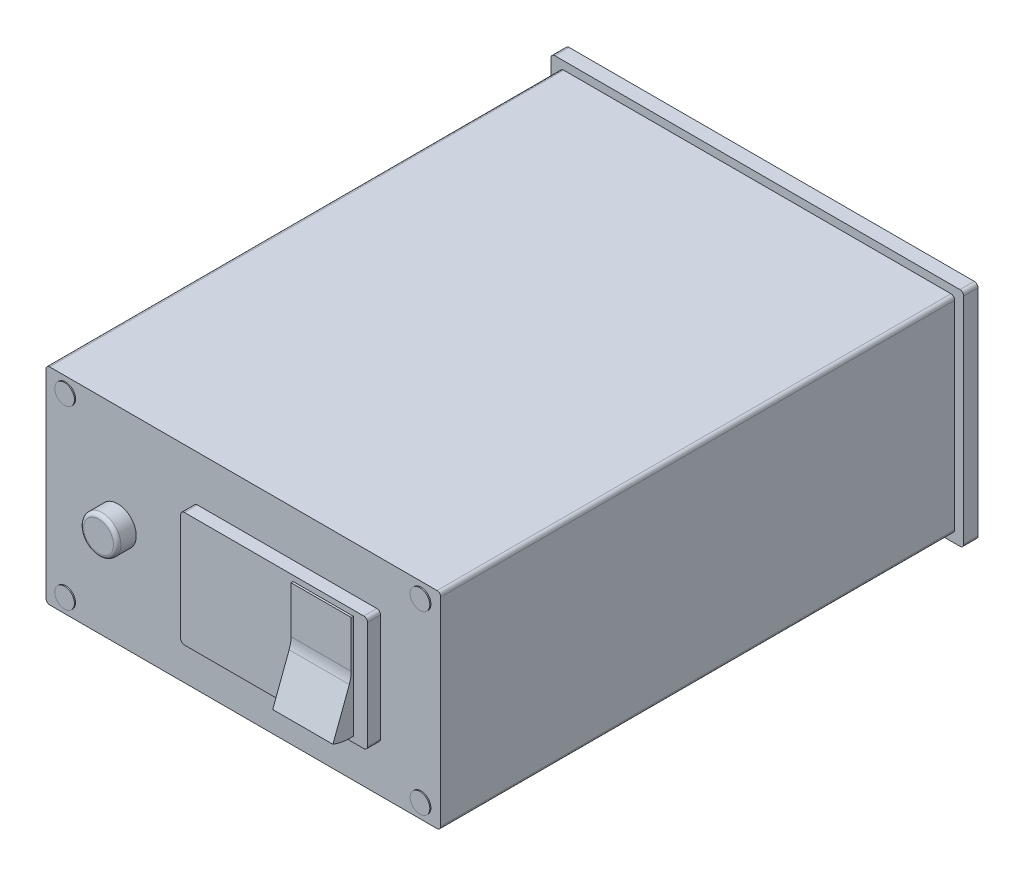
SolidWorks part; units mm, degrees
ref_plane "Front" through (0, 0, 0) normal (0, 0, 1) x (1, 0, 0)
ref_plane "Top" through (0, 0, 0) normal (0, 1, 0) x (1, 0, 0)
ref_plane "Right" through (0, 0, 0) normal (1, 0, 0) x (0, 0, -1)
sketch "Sketch1" plane through (0, 0, 0) normal (0, 0, 1) x (1, 0, 0)
  line L1 (-55.53, -29.925) -> (55.53, -29.925)
  line L2 (-55.53, -29.925) -> (-55.53, 29.925)
  line L3 (-55.53, 29.925) -> (55.53, 29.925)
  line L4 (55.53, -29.925) -> (55.53, 29.925)
  line L5 (-55.53, -29.925) -> (55.53, 29.925) construction
  line L6 (-55.53, 29.925) -> (55.53, -29.925) construction
  point P0 (0, 0)
  dimension "D1" = 59.85
  dimension "D2" = 111.06
extrude "Face" add sketch "Sketch1" along normal blind 3.86
fillet "Face Fillets" radius 1 4 edges at (-55.53, 29.925, 1.93) (-55.53, -29.925, 1.93) (55.53, -29.925, 1.93) (55.53, 29.925, 1.93)
sketch "Sketch2" plane through (0, 0, 0) normal (0, 0, 1) x (1, 0, 0)
  line L1 (-53.125, -27.75) -> (53.125, -27.75)
  line L2 (-53.125, -27.75) -> (-53.125, 27.75)
  line L3 (-53.125, 27.75) -> (53.125, 27.75)
  line L4 (53.125, -27.75) -> (53.125, 27.75)
  line L5 (-53.125, -27.75) -> (53.125, 27.75) construction
  line L6 (-53.125, 27.75) -> (53.125, -27.75) construction
  point P0 (0, 0)
  dimension "D1" = 106.25
  dimension "D2" = 55.5
extrude "Body" add sketch "Sketch2" along normal blind 142.2
sketch "Sketch3" plane through (0, -27.75, 0) normal (0, -1, 0) x (1, 0, 0)
  line L0 (-54.53, 3.86) -> (54.53, 3.86) construction
  line L1 (-36.625, 18.86) -> (36.625, 18.86) construction
  line L2 (-36.625, 18.86) -> (-36.625, 123.95) construction
  line L3 (-36.625, 123.95) -> (36.625, 123.95) construction
  line L4 (36.625, 18.86) -> (36.625, 123.95) construction
  line L5 (-36.625, 18.86) -> (36.625, 123.95) construction
  line L6 (-36.625, 123.95) -> (36.625, 18.86) construction
  line L7 (-53.125, 142.2) -> (53.125, 142.2) construction
  line L9 (-43, 117.575) -> (-30.25, 117.575)
  line L10 (-43, 117.575) -> (-43, 130.325)
  line L11 (-43, 130.325) -> (-30.25, 130.325)
  line L12 (-30.25, 117.575) -> (-30.25, 130.325)
  line L13 (-43, 117.575) -> (-30.25, 130.325) construction
  line L14 (-43, 130.325) -> (-30.25, 117.575) construction
  line L15 (30.25, 117.575) -> (43, 117.575)
  line L16 (30.25, 117.575) -> (30.25, 130.325)
  line L17 (30.25, 130.325) -> (43, 130.325)
  line L18 (43, 117.575) -> (43, 130.325)
  line L19 (30.25, 117.575) -> (43, 130.325) construction
  line L20 (30.25, 130.325) -> (43, 117.575) construction
  line L21 (30.25, 12.485) -> (43, 12.485)
  line L22 (30.25, 12.485) -> (30.25, 25.235)
  line L23 (30.25, 25.235) -> (43, 25.235)
  line L24 (43, 12.485) -> (43, 25.235)
  line L25 (30.25, 12.485) -> (43, 25.235) construction
  line L26 (30.25, 25.235) -> (43, 12.485) construction
  line L27 (-43, 12.485) -> (-30.25, 12.485)
  line L28 (-43, 12.485) -> (-43, 25.235)
  line L29 (-43, 25.235) -> (-30.25, 25.235)
  line L30 (-30.25, 12.485) -> (-30.25, 25.235)
  line L31 (-43, 12.485) -> (-30.25, 25.235) construction
  line L32 (-43, 25.235) -> (-30.25, 12.485) construction
  point P0 (0, 71.405)
  dimension "D1" = 15
  dimension "D2" = 18.25
  dimension "D3" = 73.25
  dimension "D4" = 12.75
extrude "Feet" add sketch "Sketch3" along normal blind 3.33 draft 25
fillet "Body Fillets" radius 1 4 edges at (53.125, 27.75, 73.03) (53.125, -27.75, 73.03) (-53.125, -27.75, 73.03) (-53.125, 27.75, 73.03)
sketch "Sketch4" plane through (0, 0, 142.2) normal (0, 0, 1) x (1, 0, 0)
  line L0 (-53.125, 26.75) -> (-53.125, -26.75) construction
  circle A0 centre (-33.825, 0) radius 5
  dimension "D1" = 10
  dimension "D2" = 19.3
extrude "GND Bannana Port" add sketch "Sketch4" along normal blind 5.15
fillet "Fillet3" radius 1 1 edges at (-28.825, 0, 147.35)
sketch "Sketch5" plane through (0, 0, 142.2) normal (0, 0, 1) x (1, 0, 0)
  line L0 (53.125, -26.75) -> (53.125, 26.75) construction
  line L1 (-13.375, -15.45) -> (36.925, -15.45)
  line L2 (-13.375, -15.45) -> (-13.375, 15.45)
  line L3 (-13.375, 15.45) -> (36.925, 15.45)
  line L4 (36.925, -15.45) -> (36.925, 15.45)
  line L5 (-13.375, -15.45) -> (36.925, 15.45) construction
  line L6 (-13.375, 15.45) -> (36.925, -15.45) construction
  point P0 (11.775, 0)
  dimension "D1" = 50.3
  dimension "D2" = 30.9
  dimension "D3" = 16.2
extrude "Power Port" add sketch "Sketch5" along normal blind 3.5
fillet "Fillet4" radius 1 4 edges at (-13.375, 15.45, 143.95) (-13.375, -15.45, 143.95) (36.925, -15.45, 143.95) (36.925, 15.45, 143.95)
ref_plane "Switch Plane" through (25, 0, 0) normal (1, 0, 0) x (0, 0, -1)
sketch "Sketch6" plane through (25, 0, 0) normal (1, 0, 0) x (0, 0, -1)
  line L0 (-146.274, 14) -> (-146.274, 1.4325)
  line L1 (-146.787, -1.3862) -> (-151.2, -13.1082)
  line L2 (-146.2832, 0) -> (-146.4033, 0) construction
  line L3 (-145.7, -14.45) -> (-145.7, 14.45) construction
  circle A0 centre (-146.2832, 0) radius 14 construction
  arc A1 (-146.274, 1.4325) -> (-146.787, -1.3862) centre (-154.274, 1.4325) cw
  arc A2 (-146.274, 14) -> (-151.2, -13.1082) centre (-146.2832, 0) cw
  point P4 (0, 0)
  point P8 (-146.259, 12.899)
  dimension "D1" = 28
  dimension "D2" = 8
  dimension "D3" = 5.5
extrude "Boss-Extrude6" add sketch "Sketch6" along normal mid plane 16.2
sketch "Sketch7" plane through (0, 0, 0) normal (0, 0, -1) x (-1, 0, 0)
  line L0 (-55.53, -28.925) -> (-55.53, 28.925) construction
  line L1 (54.53, -29.925) -> (-54.53, -29.925) construction
  circle A0 centre (-34.53, -2.925) radius 6.5
  dimension "D1" = 13
  dimension "D2" = 21
  dimension "D3" = 27
extrude "Boss-Extrude7" add sketch "Sketch7" along normal mid plane 4.7
sketch "Sketch8" plane through (0, 0, 142.2) normal (0, 0, 1) x (1, 0, 0)
  line L0 (-53.125, 26.75) -> (-53.125, -26.75) construction
  line L1 (52.125, 27.75) -> (-52.125, 27.75) construction
  circle A0 centre (-47.825, 23.75) radius 2.65
  point P2 (-49.1084, 24.6056)
  dimension "D1" = 5.3
  dimension "D2" = 5.3
  dimension "D3" = 4
extrude "Boss-Extrude8" add sketch "Sketch8" along normal mid plane 0.6
mirror "Mirror1" about plane through (0, 0, 0) normal (1, 0, 0) of "Boss-Extrude8"
mirror "Mirror2" about plane through (0, 0, 0) normal (0, 1, 0) of "Mirror1"
ref_plane "Plane2" through (0, -19, 0) normal (0, 1, 0) x (1, 0, 0)
sketch "Aligner Guide" plane through (0, -19, 0) normal (0, 1, 0) x (1, 0, 0)
  line L0 (-27.6997, 0.4) -> (25.0059, 0.4)
  line L1 (54.53, 0) -> (-54.53, 0) construction
  line L2 (53.525, -10.1769) -> (53.525, -139.7462)
  line L3 (-53.525, -10.1769) -> (-53.525, -139.7462)
  line L4 (-29.1637, -142.6) -> (31.0456, -142.6)
  line L5 (52.125, -142.2) -> (-52.125, -142.2) construction
  line L6 (-53.125, -142.2) -> (-53.125, -3.86) construction
  line L7 (53.125, -3.86) -> (53.125, -142.2) construction
  point P16 (-53.525, -10.1769)
  point P17 (53.525, -10.1769)
  point P18 (0, 0)
  point P19 (0, 0)
  point P20 (53.525, -139.7462)
  dimension "D1" = 0.4
  dimension "D2" = 0.4
  dimension "D3" = 0.4
  dimension "D4" = 0.4
